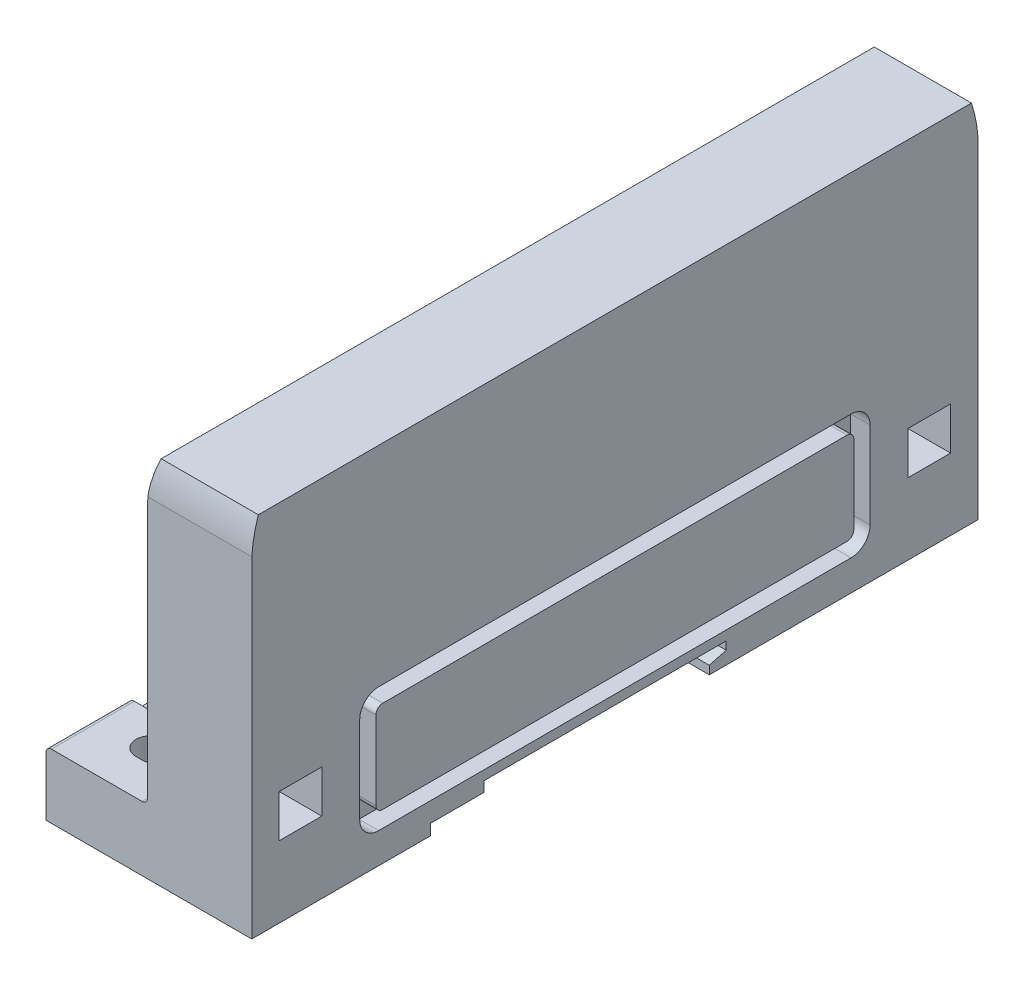
SolidWorks part; units mm, degrees
ref_plane "Front Plane" through (0, 0, 0) normal (0, 0, 1) x (1, 0, 0)
ref_plane "Top Plane" through (0, 0, 0) normal (0, 1, 0) x (1, 0, 0)
ref_plane "Right Plane" through (0, 0, 0) normal (1, 0, 0) x (0, 0, -1)
ref_plane "Plane1" through (0, 0, 0) normal (0, 0, 1) x (1, 0, 0)
sketch "Sketch1" plane through (0, 0, 0) normal (0, 0, 1) x (1, 0, 0)
  line L0 (-30.4, 10) -> (-30.4, 1.3)
  line L1 (-30.4, 1.3) -> (0, 1.3)
  line L2 (0, 1.3) -> (0, 55.1)
  line L3 (0, 55.1) -> (-14.3484, 55.1)
  line L4 (-15.4, 48.7) -> (-15.4, 11.6)
  line L5 (-16.2, 10.8) -> (-29.6, 10.8)
  arc A0 (-14.3484, 55.1) -> (-15.4, 48.7) centre (4.6, 48.7) ccw
  arc A1 (-15.4, 11.6) -> (-16.2, 10.8) centre (-16.2, 11.6) cw
  arc A2 (-29.6, 10.8) -> (-30.4, 10) centre (-29.6, 10) ccw
extrude "Boss-Extrude1" add sketch "Sketch1" against normal blind 53.65 and the other way blind 53.65
ref_plane "Plane2" through (0, 0, 0) normal (1, 0, 0) x (0, 0, -1)
sketch "Sketch2" plane through (0, 0, 0) normal (1, 0, 0) x (0, 0, -1)
  line L0 (-37.7, 21.4) -> (-37.7, 8.6)
  line L1 (-34.9, 5.8) -> (34.9, 5.8)
  line L2 (37.7, 8.6) -> (37.7, 21.4)
  line L3 (34.9, 24.2) -> (-34.9, 24.2)
  arc A0 (-37.7, 8.6) -> (-34.9, 5.8) centre (-34.9, 8.6) ccw
  arc A1 (34.9, 5.8) -> (37.7, 8.6) centre (34.9, 8.6) ccw
  arc A2 (37.7, 21.4) -> (34.9, 24.2) centre (34.9, 21.4) ccw
  arc A3 (-34.9, 24.2) -> (-37.7, 21.4) centre (-34.9, 21.4) ccw
extrude "Cut-Extrude1" cut sketch "Sketch2" against normal blind 2.9 and the other way blind 2.9
ref_plane "Plane3" through (0, 0, 0) normal (1, 0, 0) x (0, 0, -1)
sketch "Sketch3" plane through (0, 0, 0) normal (1, 0, 0) x (0, 0, -1)
  line L0 (-35.3, 20.8) -> (-35.3, 9.2)
  line L1 (-34.3, 8.2) -> (34.3, 8.2)
  line L2 (35.3, 9.2) -> (35.3, 20.8)
  line L3 (34.3, 21.8) -> (-34.3, 21.8)
  arc A0 (-35.3, 9.2) -> (-34.3, 8.2) centre (-34.3, 9.2) ccw
  arc A1 (34.3, 8.2) -> (35.3, 9.2) centre (34.3, 9.2) ccw
  arc A2 (35.3, 20.8) -> (34.3, 21.8) centre (34.3, 20.8) ccw
  arc A3 (-34.3, 21.8) -> (-35.3, 20.8) centre (-34.3, 20.8) ccw
extrude "Boss-Extrude2" add sketch "Sketch3" against normal blind 2.9
ref_plane "Plane4" through (0, 0, 0) normal (1, 0, 0) x (0, 0, -1)
sketch "Sketch4" plane through (0, 0, 0) normal (1, 0, 0) x (0, 0, -1)
  line L0 (-60, 30) -> (-53.7, 30)
  line L1 (-53.7, 30) -> (-53.7, 48.8)
  line L2 (-52.6456, 55.2) -> (52.6456, 55.2)
  line L3 (53.7, 48.8) -> (53.7, 30)
  line L4 (53.7, 30) -> (60, 30)
  line L5 (60, 30) -> (60, 66)
  line L6 (60, 66) -> (-60, 66)
  line L7 (-60, 66) -> (-60, 30)
  arc A0 (-53.7, 48.8) -> (-52.6456, 55.2) centre (-33.75, 48.8) cw
  arc A1 (52.6456, 55.2) -> (53.7, 48.8) centre (33.75, 48.8) cw
extrude "Cut-Extrude2" cut sketch "Sketch4" against normal blind 40 and the other way blind 40
ref_plane "Plane5" through (0, 0, 0) normal (1, 0, 0) x (0, 0, -1)
sketch "Sketch5" plane through (0, 0, 0) normal (1, 0, 0) x (0, 0, -1)
  line L0 (-27.25, -8.5094) -> (13.95, -8.0874)
  line L1 (13.95, -8.0874) -> (13.95, 2.5301)
  line L2 (13.95, 2.5301) -> (16.45, 3.2)
  line L3 (16.45, 3.2) -> (16.45, 4.4)
  line L4 (16.45, 4.4) -> (-19.35, 4.4)
  line L5 (-19.35, 4.4) -> (-19.35, 2.9)
  line L6 (-19.35, 2.9) -> (-27.25, 2.9)
  line L7 (-27.25, 2.9) -> (-27.25, -8.5094)
extrude "Cut-Extrude3" cut sketch "Sketch5" against normal blind 40 and the other way blind 40
ref_plane "Plane6" through (0, 0, 0) normal (0, 1, 0) x (1, 0, 0)
sketch "Sketch6" plane through (0, 0, 0) normal (0, 1, 0) x (1, 0, 0)
  line L0 (-24.45, 26.9) -> (-22.95, 26.9)
  line L1 (-22.95, 33.5) -> (-24.45, 33.5)
  arc A0 (-24.45, 33.5) -> (-24.45, 26.9) centre (-24.45, 30.2) ccw
  arc A1 (-22.95, 26.9) -> (-22.95, 33.5) centre (-22.95, 30.2) ccw
extrude "Cut-Extrude4" cut sketch "Sketch6" against normal blind 30 and the other way blind 30
ref_plane "Plane7" through (0, 0, 0) normal (0, 1, 0) x (1, 0, 0)
sketch "Sketch7" plane through (0, 0, 0) normal (0, 1, 0) x (1, 0, 0)
  line L0 (-24.45, 39.85) -> (-22.95, 39.85)
  line L1 (-22.95, 46.45) -> (-24.45, 46.45)
  arc A0 (-24.45, 46.45) -> (-24.45, 39.85) centre (-24.45, 43.15) ccw
  arc A1 (-22.95, 39.85) -> (-22.95, 46.45) centre (-22.95, 43.15) ccw
extrude "Cut-Extrude5" cut sketch "Sketch7" against normal blind 30 and the other way blind 30
ref_plane "Plane8" through (0, 0, 0) normal (0, 1, 0) x (1, 0, 0)
sketch "Sketch8" plane through (0, 0, 0) normal (0, 1, 0) x (1, 0, 0)
  line L0 (-24.45, -38.1) -> (-22.95, -38.1)
  line L1 (-22.95, -31.5) -> (-24.45, -31.5)
  arc A0 (-24.45, -31.5) -> (-24.45, -38.1) centre (-24.45, -34.8) ccw
  arc A1 (-22.95, -38.1) -> (-22.95, -31.5) centre (-22.95, -34.8) ccw
extrude "Cut-Extrude6" cut sketch "Sketch8" along normal blind 30
ref_plane "Plane9" through (0, 0, 0) normal (0, 1, 0) x (1, 0, 0)
sketch "Sketch9" plane through (0, 0, 0) normal (0, 1, 0) x (1, 0, 0)
  line L0 (-22.4, 17.95) -> (-21.4, 17.95)
  line L1 (-21.4, 22.35) -> (-22.4, 22.35)
  arc A0 (-22.4, 22.35) -> (-22.4, 17.95) centre (-22.4, 20.15) ccw
  arc A1 (-21.4, 17.95) -> (-21.4, 22.35) centre (-21.4, 20.15) ccw
extrude "Cut-Extrude7" cut sketch "Sketch9" along normal blind 30
ref_plane "Plane10" through (0, 0, 0) normal (0, 1, 0) x (1, 0, 0)
sketch "Sketch10" plane through (0, 0, 0) normal (0, 1, 0) x (1, 0, 0)
  line L0 (-22.4, -48.35) -> (-21.4, -48.35)
  line L1 (-21.4, -43.95) -> (-22.4, -43.95)
  arc A0 (-22.4, -43.95) -> (-22.4, -48.35) centre (-22.4, -46.15) ccw
  arc A1 (-21.4, -48.35) -> (-21.4, -43.95) centre (-21.4, -46.15) ccw
extrude "Cut-Extrude8" cut sketch "Sketch10" along normal blind 30
ref_plane "Plane11" through (0, 0, 0) normal (0, 1, 0) x (1, 0, 0)
sketch "Sketch11" plane through (0, 0, 0) normal (0, 1, 0) x (1, 0, 0)
  circle A0 centre (-21.45, -23.05) radius 2.15
extrude "Cut-Extrude9" cut sketch "Sketch11" along normal blind 30
ref_plane "Plane12" through (0, 10.8, 0) normal (0, 1, 0) x (1, 0, 0)
sketch "Sketch12" plane through (0, 10.8, 0) normal (0, 1, 0) x (1, 0, 0)
  line L0 (-31, 36.8) -> (-31, 23.6)
  line L1 (-31, 23.6) -> (-22.9, 23.6)
  line L2 (-22.9, 36.8) -> (-31, 36.8)
  arc A0 (-22.9, 23.6) -> (-22.9, 36.8) centre (-22.9, 30.2) ccw
extrude "Cut-Extrude10" cut sketch "Sketch12" against normal blind 2
ref_plane "Plane13" through (0, 10.8, 0) normal (0, 1, 0) x (1, 0, 0)
sketch "Sketch13" plane through (0, 10.8, 0) normal (0, 1, 0) x (1, 0, 0)
  line L0 (-31, 49.75) -> (-31, 36.55)
  line L1 (-31, 36.55) -> (-22.9, 36.55)
  line L2 (-22.9, 49.75) -> (-31, 49.75)
  arc A0 (-22.9, 36.55) -> (-22.9, 49.75) centre (-22.9, 43.15) ccw
extrude "Cut-Extrude11" cut sketch "Sketch13" against normal blind 2
ref_plane "Plane14" through (0, 10.8, 0) normal (0, 1, 0) x (1, 0, 0)
sketch "Sketch14" plane through (0, 10.8, 0) normal (0, 1, 0) x (1, 0, 0)
  line L0 (-31, -28.2) -> (-31, -41.4)
  line L1 (-31, -41.4) -> (-22.9, -41.4)
  line L2 (-22.9, -28.2) -> (-31, -28.2)
  arc A0 (-22.9, -41.4) -> (-22.9, -28.2) centre (-22.9, -34.8) ccw
extrude "Cut-Extrude12" cut sketch "Sketch14" against normal blind 2
ref_plane "Plane15" through (0, 0, 0) normal (1, 0, 0) x (0, 0, -1)
sketch "Sketch15" plane through (0, 0, 0) normal (1, 0, 0) x (0, 0, -1)
  line L0 (43.3, 18.15) -> (43.3, 11.85)
  line L1 (43.3, 11.85) -> (49.6, 11.85)
  line L2 (49.6, 11.85) -> (49.6, 18.15)
  line L3 (49.6, 18.15) -> (43.3, 18.15)
extrude "Cut-Extrude13" cut sketch "Sketch15" against normal blind 9.4
ref_plane "Plane16" through (0, 15, 0) normal (0, 1, 0) x (1, 0, 0)
sketch "Sketch16" plane through (0, 15, 0) normal (0, 1, 0) x (1, 0, 0)
  line L0 (-17.4, 46.45) -> (-17.4, 50.45)
  line L1 (-17.4, 50.45) -> (-12.4, 50.45)
  line L2 (-12.4, 50.45) -> (-12.4, 48.95)
  line L3 (-12.4, 48.95) -> (-9.4, 48.95)
  line L4 (-9.4, 48.95) -> (-9.4, 46.45)
  line L5 (-9.4, 46.45) -> (-17.4, 46.45)
  line L6 (0, 46.45) -> (-15.4, 46.45) construction
revolve "Cut-Revolve1" cut sketch "Sketch16" angle 360 about L6 reverse direction yes
ref_plane "Plane17" through (0, 0, 0) normal (1, 0, 0) x (0, 0, -1)
sketch "Sketch17" plane through (0, 0, 0) normal (1, 0, 0) x (0, 0, -1)
  line L0 (-49.6, 18.15) -> (-49.6, 11.85)
  line L1 (-49.6, 11.85) -> (-43.3, 11.85)
  line L2 (-43.3, 11.85) -> (-43.3, 18.15)
  line L3 (-43.3, 18.15) -> (-49.6, 18.15)
extrude "Cut-Extrude14" cut sketch "Sketch17" against normal blind 9.4
ref_plane "Plane18" through (0, 15, 0) normal (0, 1, 0) x (1, 0, 0)
sketch "Sketch18" plane through (0, 15, 0) normal (0, 1, 0) x (1, 0, 0)
  line L0 (-17.4, -46.45) -> (-17.4, -42.45)
  line L1 (-17.4, -42.45) -> (-12.4, -42.45)
  line L2 (-12.4, -42.45) -> (-12.4, -43.95)
  line L3 (-12.4, -43.95) -> (-9.4, -43.95)
  line L4 (-9.4, -43.95) -> (-9.4, -46.45)
  line L5 (-9.4, -46.45) -> (-17.4, -46.45)
  line L6 (0, -46.45) -> (-15.4, -46.45) construction
revolve "Cut-Revolve2" cut sketch "Sketch18" angle 360 about L6 reverse direction yes
ref_plane "Plane19" through (0, 0, 0) normal (0, 1, 0) x (1, 0, 0)
sketch "Sketch19" plane through (0, 0, 0) normal (0, 1, 0) x (1, 0, 0)
  line L0 (-22.4, -49.85) -> (-21.4, -49.85)
  line L1 (-21.4, -42.45) -> (-22.4, -42.45)
  line L2 (-22.4, -48.35) -> (-21.4, -48.35)
  line L3 (-21.4, -43.95) -> (-22.4, -43.95)
  arc A0 (-22.4, -42.45) -> (-22.4, -49.85) centre (-22.4, -46.15) ccw
  arc A1 (-21.4, -49.85) -> (-21.4, -42.45) centre (-21.4, -46.15) ccw
  arc A2 (-22.4, -43.95) -> (-22.4, -48.35) centre (-22.4, -46.15) ccw
  arc A3 (-21.4, -48.35) -> (-21.4, -43.95) centre (-21.4, -46.15) ccw
extrude "Boss-Extrude3" add sketch "Sketch19" along normal blind 1.5
ref_plane "Plane20" through (0, 0, 0) normal (0, 1, 0) x (1, 0, 0)
sketch "Sketch20" plane through (0, 0, 0) normal (0, 1, 0) x (1, 0, 0)
  line L0 (-24.45, -40.1) -> (-22.95, -40.1)
  line L1 (-22.95, -29.5) -> (-24.45, -29.5)
  line L2 (-24.45, -38.1) -> (-22.95, -38.1)
  line L3 (-22.95, -31.5) -> (-24.45, -31.5)
  arc A0 (-24.45, -29.5) -> (-24.45, -40.1) centre (-24.45, -34.8) ccw
  arc A1 (-22.95, -40.1) -> (-22.95, -29.5) centre (-22.95, -34.8) ccw
  arc A2 (-24.45, -31.5) -> (-24.45, -38.1) centre (-24.45, -34.8) ccw
  arc A3 (-22.95, -38.1) -> (-22.95, -31.5) centre (-22.95, -34.8) ccw
extrude "Boss-Extrude4" add sketch "Sketch20" along normal blind 1.5
ref_plane "Plane21" through (0, 0, 0) normal (0, 1, 0) x (1, 0, 0)
sketch "Sketch21" plane through (0, 0, 0) normal (0, 1, 0) x (1, 0, 0)
  line L0 (-24.45, 24.9) -> (-22.95, 24.9)
  line L1 (-22.95, 35.5) -> (-24.45, 35.5)
  line L2 (-24.45, 26.9) -> (-22.95, 26.9)
  line L3 (-22.95, 33.5) -> (-24.45, 33.5)
  arc A0 (-24.45, 35.5) -> (-24.45, 24.9) centre (-24.45, 30.2) ccw
  arc A1 (-22.95, 24.9) -> (-22.95, 35.5) centre (-22.95, 30.2) ccw
  arc A2 (-24.45, 33.5) -> (-24.45, 26.9) centre (-24.45, 30.2) ccw
  arc A3 (-22.95, 26.9) -> (-22.95, 33.5) centre (-22.95, 30.2) ccw
extrude "Boss-Extrude5" add sketch "Sketch21" along normal blind 1.5
ref_plane "Plane22" through (0, 0, 0) normal (0, 1, 0) x (1, 0, 0)
sketch "Sketch22" plane through (0, 0, 0) normal (0, 1, 0) x (1, 0, 0)
  line L0 (-24.45, 37.85) -> (-22.95, 37.85)
  line L1 (-22.95, 48.45) -> (-24.45, 48.45)
  line L2 (-24.45, 39.85) -> (-22.95, 39.85)
  line L3 (-22.95, 46.45) -> (-24.45, 46.45)
  arc A0 (-24.45, 48.45) -> (-24.45, 37.85) centre (-24.45, 43.15) ccw
  arc A1 (-22.95, 37.85) -> (-22.95, 48.45) centre (-22.95, 43.15) ccw
  arc A2 (-24.45, 46.45) -> (-24.45, 39.85) centre (-24.45, 43.15) ccw
  arc A3 (-22.95, 39.85) -> (-22.95, 46.45) centre (-22.95, 43.15) ccw
extrude "Boss-Extrude6" add sketch "Sketch22" along normal blind 1.5
ref_plane "Plane23" through (0, 0, -4) normal (0, 0, 1) x (1, 0, 0)
sketch "Sketch23" plane through (0, 0, -4) normal (0, 0, 1) x (1, 0, 0)
  line L0 (-22.55, 11.3) -> (-18.55, 11.3)
  line L1 (-18.55, 11.3) -> (-18.05, 10.8)
  line L2 (-18.05, 10.8) -> (-22.55, 10.8)
  line L3 (-22.55, 10.8) -> (-22.55, 11.3)
  line L4 (-22.55, 10.8) -> (-22.55, 11.3) construction
revolve "Revolve1" add sketch "Sketch23" angle 360 about L4 reverse direction yes
ref_plane "Plane24" through (0, 0, -4) normal (0, 0, 1) x (1, 0, 0)
sketch "Sketch24" plane through (0, 0, -4) normal (0, 0, 1) x (1, 0, 0)
  line L0 (-22.55, 15.385) -> (-21.9834, 15.385)
  line L1 (-21.9834, 15.385) -> (-20.2514, 16.385)
  line L2 (-18.55, 15.4285) -> (-18.55, 13.8)
  line L3 (-18.55, 13.8) -> (-20.55, 13.8)
  line L4 (-20.55, 13.8) -> (-20.55, 13.7)
  line L5 (-20.55, 13.7) -> (-18.55, 13.7)
  line L6 (-18.55, 13.7) -> (-18.05, 13.2)
  line L7 (-18.05, 13.2) -> (-18.05, 12.8)
  line L8 (-18.05, 12.8) -> (-18.55, 12.8)
  line L9 (-18.55, 12.8) -> (-18.55, 11.3)
  line L10 (-18.55, 11.3) -> (-22.55, 11.3)
  line L11 (-22.55, 11.3) -> (-22.55, 15.385)
  line L12 (-22.55, 11.3) -> (-22.55, 16.385) construction
  arc A0 (-20.2514, 16.385) -> (-18.55, 15.4285) centre (-22.55, 10.305) cw
revolve "Revolve2" add sketch "Sketch24" angle 360 about L12 reverse direction yes
ref_plane "Plane25" through (-22.55, 0, 0) normal (1, 0, 0) x (0, 0, -1)
sketch "Sketch25" plane through (-22.55, 0, 0) normal (1, 0, 0) x (0, 0, -1)
  line L0 (-0.5, 10.8) -> (8.5, 10.8)
  line L1 (8.5, 10.8) -> (8, 11.3)
  line L2 (8, 11.3) -> (0, 11.3)
  line L3 (0, 11.3) -> (-0.5, 10.8)
extrude "Boss-Extrude7" add sketch "Sketch25" along normal blind 10
ref_plane "Plane26" through (0, 15.385, 0) normal (0, 1, 0) x (1, 0, 0)
sketch "Sketch26" plane through (0, 15.385, 0) normal (0, 1, 0) x (1, 0, 0)
  arc A0 (-24.4094, 3.4298) -> (-23.9735, 2.6748) centre (-24.1019, 3.104) ccw
  arc A1 (-23.9735, 2.6748) -> (-22.9859, 2.1046) centre (-23.7487, 1.9237) cw
  arc A2 (-22.9859, 2.1046) -> (-22.1141, 2.1046) centre (-22.55, 2.208) ccw
  arc A3 (-22.1141, 2.1046) -> (-21.1265, 2.6748) centre (-21.3513, 1.9237) cw
  arc A4 (-21.1265, 2.6748) -> (-20.6906, 3.4298) centre (-20.9981, 3.104) ccw
  arc A5 (-20.6906, 3.4298) -> (-20.6906, 4.5702) centre (-20.1525, 4) cw
  arc A6 (-20.6906, 4.5702) -> (-21.1265, 5.3252) centre (-20.9981, 4.896) ccw
  arc A7 (-21.1265, 5.3252) -> (-22.1141, 5.8954) centre (-21.3513, 6.0763) cw
  arc A8 (-22.1141, 5.8954) -> (-22.9859, 5.8954) centre (-22.55, 5.792) ccw
  arc A9 (-22.9859, 5.8954) -> (-23.9735, 5.3252) centre (-23.7487, 6.0763) cw
  arc A10 (-23.9735, 5.3252) -> (-24.4094, 4.5702) centre (-24.1019, 4.896) ccw
  arc A11 (-24.4094, 4.5702) -> (-24.4094, 3.4298) centre (-24.9475, 4) cw
extrude "Cut-Extrude15" cut sketch "Sketch26" along normal blind 2
ref_plane "Plane27" through (0, 0, 0) normal (0, 1, 0) x (1, 0, 0)
sketch "Sketch27" plane through (0, 0, 0) normal (0, 1, 0) x (1, 0, 0)
  line L0 (-22.4, 16.45) -> (-21.4, 16.45)
  line L1 (-21.4, 23.85) -> (-22.4, 23.85)
  line L2 (-22.4, 17.95) -> (-21.4, 17.95)
  line L3 (-21.4, 22.35) -> (-22.4, 22.35)
  arc A0 (-22.4, 23.85) -> (-22.4, 16.45) centre (-22.4, 20.15) ccw
  arc A1 (-21.4, 16.45) -> (-21.4, 23.85) centre (-21.4, 20.15) ccw
  arc A2 (-22.4, 22.35) -> (-22.4, 17.95) centre (-22.4, 20.15) ccw
  arc A3 (-21.4, 17.95) -> (-21.4, 22.35) centre (-21.4, 20.15) ccw
extrude "Boss-Extrude8" add sketch "Sketch27" along normal blind 1.5
